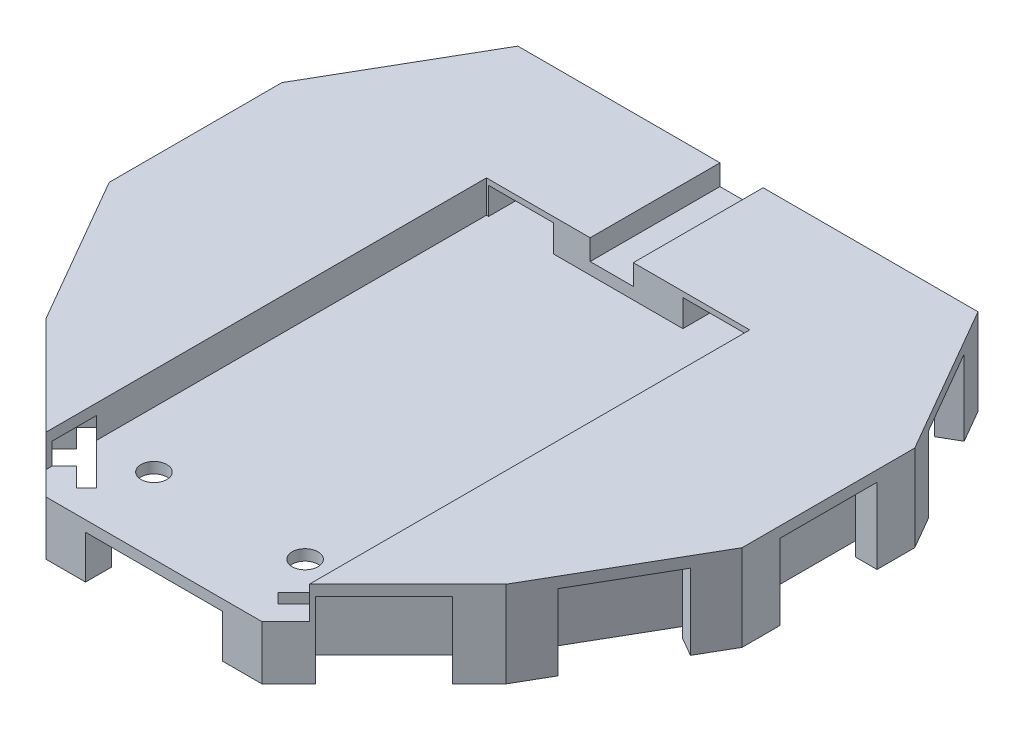
SolidWorks part; units mm, degrees
ref_plane "Front Plane" through (0, 0, 0) normal (0, 0, 1) x (1, 0, 0)
ref_plane "Top Plane" through (0, 0, 0) normal (0, 1, 0) x (1, 0, 0)
ref_plane "Right Plane" through (0, 0, 0) normal (1, 0, 0) x (0, 0, -1)
sketch "Sketch1" plane through (0, -12.45, 0) normal (0, -1, 0) x (1, 0, 0)
  line L0 (-7.62, 25.4) -> (-13.123, 25.4) construction
  line L1 (-18.0975, -36.83) -> (18.0975, -36.83) construction
  line L2 (-18.0975, -36.83) -> (-18.0975, 19.05) construction
  line L3 (-18.0975, 19.05) -> (18.0975, 19.05) construction
  line L4 (18.0975, -36.83) -> (18.0975, 19.05) construction
  line L5 (-18.0975, -36.83) -> (18.0975, 19.05) construction
  line L6 (-18.0975, 19.05) -> (18.0975, -36.83) construction
  line L7 (0, 0) -> (0, 31.75) construction
  line L8 (-12.7, 31.75) -> (12.7, 31.75)
  line L9 (12.7, 31.75) -> (27.0684, 17.3816)
  line L10 (-12.7, 31.75) -> (-27.0684, 17.3816)
  line L11 (27.0684, 17.3816) -> (37.2284, -0.216)
  line L12 (-27.0684, 17.3816) -> (-37.2284, -0.216)
  line L13 (37.2284, -0.216) -> (37.2284, -20.536)
  line L14 (-37.2284, -0.216) -> (-37.2284, -20.536)
  line L15 (37.2284, -20.536) -> (27.0684, -38.1337)
  line L16 (-37.2284, -20.536) -> (-27.0684, -38.1337)
  line L17 (14.047, 26.8109) -> (22.1293, 18.7286)
  line L18 (14.047, 26.8109) -> (17.6391, 30.403)
  line L19 (22.1293, 18.7286) -> (25.7214, 22.3207)
  line L20 (17.6391, 30.403) -> (25.7214, 22.3207)
  line L21 (14.047, 26.8109) -> (25.7214, 22.3207) construction
  line L22 (22.1293, 18.7286) -> (17.6391, 30.403) construction
  line L23 (-14.047, 26.8109) -> (-25.7214, 22.3207) construction
  line L24 (-22.1293, 18.7286) -> (-17.6391, 30.403) construction
  line L25 (-14.047, 26.8109) -> (-22.1293, 18.7286)
  line L26 (-14.047, 26.8109) -> (-17.6391, 30.403)
  line L27 (-17.6391, 30.403) -> (-25.7214, 22.3207)
  line L28 (-22.1293, 18.7286) -> (-25.7214, 22.3207)
  line L29 (27.0912, 12.2621) -> (32.8062, 2.3634)
  line L30 (27.0912, 12.2621) -> (31.4906, 14.8021)
  line L31 (32.8062, 2.3634) -> (37.2056, 4.9034)
  line L32 (31.4906, 14.8021) -> (37.2056, 4.9034)
  line L33 (27.0912, 12.2621) -> (37.2056, 4.9034) construction
  line L34 (32.8062, 2.3634) -> (31.4906, 14.8021) construction
  line L35 (-27.0912, 12.2621) -> (-37.2056, 4.9034) construction
  line L36 (-32.8062, 2.3634) -> (-31.4906, 14.8021) construction
  line L37 (-27.0912, 12.2621) -> (-32.8062, 2.3634)
  line L38 (-27.0912, 12.2621) -> (-31.4906, 14.8021)
  line L39 (-31.4906, 14.8021) -> (-37.2056, 4.9034)
  line L40 (-32.8062, 2.3634) -> (-37.2056, 4.9034)
  line L41 (34.6884, -4.661) -> (34.6884, -16.091)
  line L42 (34.6884, -4.661) -> (39.7684, -4.661)
  line L43 (34.6884, -16.091) -> (39.7684, -16.091)
  line L44 (39.7684, -4.661) -> (39.7684, -16.091)
  line L45 (34.6884, -4.661) -> (39.7684, -16.091) construction
  line L46 (34.6884, -16.091) -> (39.7684, -4.661) construction
  line L47 (-34.6884, -4.661) -> (-39.7684, -16.091) construction
  line L48 (-34.6884, -16.091) -> (-39.7684, -4.661) construction
  line L49 (-34.6884, -4.661) -> (-34.6884, -16.091)
  line L50 (-34.6884, -4.661) -> (-39.7684, -4.661)
  line L51 (-39.7684, -4.661) -> (-39.7684, -16.091)
  line L52 (-34.6884, -16.091) -> (-39.7684, -16.091)
  line L53 (32.8062, -23.1155) -> (27.0912, -33.0142)
  line L54 (32.8062, -23.1155) -> (37.2056, -25.6555)
  line L55 (27.0912, -33.0142) -> (31.4906, -35.5542)
  line L56 (37.2056, -25.6555) -> (31.4906, -35.5542)
  line L57 (32.8062, -23.1155) -> (31.4906, -35.5542) construction
  line L58 (27.0912, -33.0142) -> (37.2056, -25.6555) construction
  line L59 (-32.8062, -23.1155) -> (-31.4906, -35.5542) construction
  line L60 (-27.0912, -33.0142) -> (-37.2056, -25.6555) construction
  line L61 (-32.8062, -23.1155) -> (-27.0912, -33.0142)
  line L62 (-32.8062, -23.1155) -> (-37.2056, -25.6555)
  line L63 (-37.2056, -25.6555) -> (-31.4906, -35.5542)
  line L64 (-27.0912, -33.0142) -> (-31.4906, -35.5542)
  line L65 (11.8379, 29.02) -> (24.3384, 16.5195)
  line L66 (11.8379, 29.02) -> (10.6705, 27.8526)
  line L67 (24.3384, 16.5195) -> (23.171, 15.3521)
  line L68 (10.6705, 27.8526) -> (23.171, 15.3521)
  line L69 (-11.8379, 29.02) -> (-24.3384, 16.5195)
  line L70 (-11.8379, 29.02) -> (-10.6705, 27.8526)
  line L71 (-10.6705, 27.8526) -> (-23.171, 15.3521)
  line L72 (-24.3384, 16.5195) -> (-23.171, 15.3521)
  line L73 (25.5291, 14.9677) -> (34.3683, -0.3422)
  line L74 (25.5291, 14.9677) -> (24.0993, 14.1422)
  line L75 (34.3683, -0.3422) -> (32.9385, -1.1677)
  line L76 (24.0993, 14.1422) -> (32.9385, -1.1677)
  line L77 (-25.5291, 14.9677) -> (-34.3683, -0.3422)
  line L78 (-25.5291, 14.9677) -> (-24.0993, 14.1422)
  line L79 (-24.0993, 14.1422) -> (-32.9385, -1.1677)
  line L80 (-34.3683, -0.3422) -> (-32.9385, -1.1677)
  line L81 (34.6884, -1.5368) -> (34.6884, -19.2152)
  line L82 (34.6884, -1.5368) -> (33.0374, -1.5368)
  line L83 (34.6884, -19.2152) -> (33.0374, -19.2152)
  line L84 (33.0374, -1.5368) -> (33.0374, -19.2152)
  line L85 (-34.6884, -1.5368) -> (-34.6884, -19.2152)
  line L86 (-34.6884, -1.5368) -> (-33.0374, -1.5368)
  line L87 (-33.0374, -1.5368) -> (-33.0374, -19.2152)
  line L88 (-34.6884, -19.2152) -> (-33.0374, -19.2152)
  line L89 (25.5291, -35.7198) -> (34.3683, -20.4099)
  line L90 (25.5291, -35.7198) -> (24.0993, -34.8943)
  line L91 (34.3683, -20.4099) -> (32.9385, -19.5844)
  line L92 (24.0993, -34.8943) -> (32.9385, -19.5844)
  line L93 (-25.5291, -35.7198) -> (-34.3683, -20.4099)
  line L94 (-25.5291, -35.7198) -> (-24.0993, -34.8943)
  line L95 (-24.0993, -34.8943) -> (-32.9385, -19.5844)
  line L96 (-34.3683, -20.4099) -> (-32.9385, -19.5844)
  line L97 (-27.0684, -38.1337) -> (27.0684, -38.1337)
  point P6 (19.8842, 24.5658)
  point P21 (32.1484, 8.5828)
  point P22 (37.2284, -10.376)
  point P23 (0, -8.89)
  point P32 (-19.8842, 24.5658)
  point P33 (32.1484, -29.3349)
  point P42 (-32.1484, 8.5828)
  point P52 (-37.2284, -10.376)
  point P62 (-32.1484, -29.3349)
  point P92 (18.0882, 22.7697)
  point P93 (29.9487, 7.3128)
  point P94 (34.6884, -10.376)
  point P95 (29.9487, -28.0649)
  line M56 (15.24, 25.4) -> (7.62, 25.4)
  line M57 (7.62, 25.4) -> (7.62, 23.7024)
  arc M58 (7.62, 23.7024) -> (7.62, 22.0176) centre (8.89, 22.86) cw
  line M59 (7.62, 22.0176) -> (7.62, -22.86)
  line M60 (7.62, -22.86) -> (15.24, -22.86)
  line M61 (15.24, -22.86) -> (15.24, 25.4)
  dimension "D1" = 55.88
  dimension "D2" = 36.195
  dimension "D3" = 6.35
  dimension "D4" = 45
  dimension "D5" = 30
  dimension "D6" = 30
  dimension "D7" = 20.32
  dimension "D8" = 6.35
  dimension "D9" = 11.43
  dimension "D10" = 2.54
  dimension "D11" = 17.6784
  dimension "D12" = 1.651
  dimension "D13" = 25.4
extrude "Boss-Extrude1" add sketch "Sketch1" against normal blind 3.81 contours L16 L97 L15 L55 L89 L90 L92 L91 L54 L13 L43 L81 L83 L84 L82 L42 L11 L31 L73 L75 L76 L74 L30 L9 L19 L65 L67 L68 L66 L18 L8 L10 L26 L69 L70 L71 M61 M60 M59 M58 M57 M56 | L85 L88 L87 L86 L49 | L52 L49 L50 L14 | L77 L80 L79 L78 L37 | L40 L37 L38 L12 | L69 L72 L71 L70 L25 | L28 L25 L26 L10 | L68 M56 M57 M58 M59 M60 M61 | L68 M56 M61 | L66 L68 L67 L65 L17 M56 M61 | L17 L19 L9 L18 | L74 L76 L75 L73 L29 | L29 L31 L11 L30 | L82 L84 L83 L81 L41 | L41 L43 L13 L42 | L92 L90 L89 L53 L91 | L53 L55 L15 L54 | L96 L93 L61 L94 L95 | L64 L61 L62 L16 region at (-1.166, -12.45, -7.077) region at (-18.9862, -12.45, 23.6678) region at (18.9862, -12.45, 23.6678) region at (-17.5044, -12.45, 22.186) region at (17.7514, -12.45, 21.9774) region at (-31.0486, -12.45, 7.9478) region at (31.0486, -12.45, 7.9478) region at (-29.2338, -12.45, 6.9) region at (29.2338, -12.45, 6.9) region at (14.5343, -12.45, 24.6943) region at (11.4591, -12.45, 0.7016) region at (-35.9584, -12.45, -10.376) region at (35.9584, -12.45, -10.376) region at (-33.8629, -12.45, -10.376) region at (33.8629, -12.45, -10.376) region at (-31.0486, -12.45, -28.6999) region at (31.0486, -12.45, -28.6999) region at (-29.2338, -12.45, -27.6521) region at (29.2338, -12.45, -27.6521)
sketch "Sketch2" plane through (0, -12.45, 0) normal (0, -1, 0) x (1, 0, 0)
  line L0 (-7.62, 25.4) -> (-13.123, 25.4) construction
  line L1 (-15.24, 25.4) -> (15.24, 25.4)
  line L2 (-15.24, 25.4) -> (-15.24, -22.86)
  line L3 (-15.24, -22.86) -> (15.24, -22.86)
  line L4 (15.24, 25.4) -> (15.24, -22.86)
  line L5 (-15.24, 23.283) -> (-15.24, -22.86) construction
extrude "Cut-Extrude1" cut sketch "Sketch2" against normal blind 3.81
sketch "Sketch4" plane through (0, 0, 25.4) normal (0, 0, -1) x (-1, 0, 0)
  line L4 (-15.24, -12.45) -> (15.24, -12.45)
  line L5 (15.24, -12.45) -> (15.24, -8.64)
  line L6 (15.24, -8.64) -> (-15.24, -8.64)
  line L7 (-15.24, -8.64) -> (-15.24, -12.45)
  line L8 (-15.24, -12.45) -> (15.24, -12.45)
  line L9 (15.24, -12.45) -> (15.24, -8.64)
  line L10 (15.24, -8.64) -> (-15.24, -8.64)
  line L11 (-15.24, -8.64) -> (-15.24, -12.45)
  dimension "D1" = 0
extrude "Cut-Extrude2" cut sketch "Sketch4" against normal blind 27.94
sketch "Sketch5" plane through (0, 0, -22.86) normal (0, 0, 1) x (1, 0, 0)
  line L1 (-15.24, -8.64) -> (-15.49, -8.64)
  line L2 (-15.24, -8.64) -> (-15.24, -12.45)
  line L3 (-15.24, -12.45) -> (-15.49, -12.45)
  line L4 (-15.24, -12.45) -> (15.24, -12.45)
  line L5 (15.24, -12.45) -> (15.24, -8.64)
  line L6 (15.24, -8.64) -> (-15.24, -8.64)
  line L7 (-15.24, -8.64) -> (-15.24, -12.45)
  line L8 (-15.24, -12.45) -> (15.24, -12.45)
  line L9 (15.24, -12.45) -> (15.24, -8.64)
  line L10 (15.24, -8.64) -> (-15.24, -8.64)
  line L11 (-15.24, -8.64) -> (-15.24, -12.45)
  line L12 (-15.49, -8.64) -> (-15.49, -12.45)
  line L13 (15.24, -8.64) -> (15.49, -8.64)
  line L14 (15.24, -8.64) -> (15.24, -12.45)
  line L15 (15.24, -12.45) -> (15.49, -12.45)
  line L16 (15.49, -8.64) -> (15.49, -12.45)
  line M13 (-15.24, -8.64) -> (-15.24, -12.45)
  dimension "D2" = 0.25
  dimension "D3" = 0.25
  dimension "D1" = 0
extrude "Cut-Extrude3" cut sketch "Sketch5" along normal through all contours L1 L12 L3 M13 | L13 L16 L15 L14 region at (-15.365, -10.545, -22.86)
sketch "Sketch6" plane through (0, 0, -22.86) normal (0, 0, 1) x (1, 0, 0)
  line L0 (7.62, -12.45) -> (15.24, -12.45) construction
  line L1 (15.24, -9.275) -> (15.24, -12.45) construction
  line L2 (11.557, -9.275) -> (15.24, -9.275) construction
  line L3 (11.557, -9.275) -> (7.62, -9.275) construction
  line L4 (7.62, -9.275) -> (7.62, -12.45) construction
  line L5 (-15.24, -12.45) -> (-15.24, -9.275) construction
  line L6 (-15.24, -9.275) -> (-11.557, -9.275) construction
  line L7 (-11.557, -9.275) -> (-7.62, -9.275) construction
  line L8 (-7.62, -9.275) -> (-7.62, -12.45) construction
  line L9 (-15.24, -12.45) -> (-7.62, -12.45) construction
  line L10 (7.62, -12.45) -> (15.24, -12.45)
  line L11 (15.24, -9.275) -> (15.24, -12.45)
  line L12 (11.557, -9.275) -> (15.24, -9.275)
  line L13 (11.557, -9.275) -> (7.62, -9.275)
  line L14 (7.62, -9.275) -> (7.62, -12.45)
  line L15 (-15.24, -12.45) -> (-15.24, -9.275)
  line L16 (-15.24, -9.275) -> (-11.557, -9.275)
  line L17 (-11.557, -9.275) -> (-7.62, -9.275)
  line L18 (-7.62, -9.275) -> (-7.62, -12.45)
  line L19 (-15.24, -12.45) -> (-7.62, -12.45)
extrude "Cut-Extrude4" cut sketch "Sketch6" against normal blind 7.874
extrude "Boss-Extrude2" add sketch "Sketch1<3>" along normal blind 1.27 contours L8 L9 L11 L13 L15 L97 L16 L14 L12 L10
sketch "Sketch1<3>" plane through (0, -12.45, 0) normal (0, -1, 0) x (1, 0, 0) same geometry as "Sketch1"
sketch "Sketch7" plane through (0, -13.72, 0) normal (0, -1, 0) x (1, 0, 0)
  line L0 (0, 0) -> (0, 31.75) construction
  line L1 (0, 0) -> (0, 31.75)
  line L2 (-24.0993, -34.8943) -> (-32.9385, -19.5844) construction
  line L3 (-33.0374, -1.5368) -> (-33.0374, -19.2152) construction
  line L4 (-24.0993, 14.1422) -> (-32.9385, -1.1677) construction
  line L5 (-10.6705, 27.8526) -> (-23.171, 15.3521) construction
  line L6 (-8.043, 28.6839) -> (-8.043, 31.75)
  line L7 (-9.7724, 26.9545) -> (-8.043, 28.6839)
  line L8 (-9.7724, 26.9545) -> (-22.6985, 14.0285)
  line L9 (-22.6985, 14.0285) -> (-31.7674, -1.6793)
  line L10 (-31.7674, -1.6793) -> (-31.7674, -19.0728)
  line L11 (-20.7626, -38.1337) -> (-31.7674, -19.0728)
  line L12 (8.043, 28.6839) -> (8.043, 31.75)
  line L13 (9.7724, 26.9545) -> (8.043, 28.6839)
  line L14 (9.7724, 26.9545) -> (22.6985, 14.0285)
  line L15 (22.6985, 14.0285) -> (31.7674, -1.6793)
  line L16 (31.7674, -1.6793) -> (31.7674, -19.0728)
  line L17 (20.7626, -38.1337) -> (31.7674, -19.0728)
  line L18 (20.7626, -38.1337) -> (27.0684, -38.1337)
  line L19 (20.7626, -38.1337) -> (27.0684, -38.1337)
  line L20 (-8.043, 31.75) -> (-12.7, 31.75)
  line L21 (-21.1292, -37.4987) -> (-31.7674, -19.0728) construction
  line L23 (-12.7, 31.75) -> (-27.0684, 17.3816)
  line L24 (-27.0684, 17.3816) -> (-37.2284, -0.216)
  line L25 (-22.2291, -38.1337) -> (-33.0374, -19.4131) construction
  line L26 (-33.0374, -1.339) -> (-33.0374, -19.4131) construction
  line L27 (-23.7148, 14.8083) -> (-33.0374, -1.339) construction
  line L28 (-10.6705, 27.8526) -> (-23.7148, 14.8083)
  line L29 (-10.6705, 27.8526) -> (-9.313, 29.21) construction
  line L31 (-9.313, 29.21) -> (-9.313, 31.75) construction
  line L32 (-12.7, 31.75) -> (12.7, 31.75) construction
  line L34 (-27.0684, -38.1337) -> (27.0684, -38.1337) construction
  line L35 (-27.0684, -38.1337) -> (-20.7626, -38.1337)
  line L36 (-37.2284, -0.216) -> (-37.2284, -20.536)
  line L37 (-37.2284, -20.536) -> (-27.0684, -38.1337)
  line L38 (-27.0684, -38.1337) -> (27.0684, -38.1337)
  line L39 (27.0684, -38.1337) -> (37.2284, -20.536)
  line L40 (37.2284, -20.536) -> (37.2284, -0.216)
  line L41 (37.2284, -0.216) -> (27.0684, 17.3816)
  line L42 (27.0684, 17.3816) -> (12.7, 31.75)
  line L43 (12.7, 31.75) -> (-12.7, 31.75)
  line L44 (-12.7, 31.75) -> (-27.0684, 17.3816)
  line L45 (-27.0684, 17.3816) -> (-37.2284, -0.216)
  line L46 (-37.2284, -0.216) -> (-37.2284, -20.536)
  line L47 (-37.2284, -20.536) -> (-27.0684, -38.1337)
  line L48 (-27.0684, -38.1337) -> (-20.7626, -38.1337)
  line L49 (27.0684, -38.1337) -> (37.2284, -20.536)
  line L50 (37.2284, -20.536) -> (37.2284, -0.216)
  line L51 (37.2284, -0.216) -> (27.0684, 17.3816)
  line L52 (27.0684, 17.3816) -> (12.7, 31.75)
  line L53 (12.7, 31.75) -> (8.043, 31.75)
  line M19 (-27.0684, -38.1337) -> (27.0684, -38.1337)
  line M20 (27.0684, -38.1337) -> (37.2284, -20.536)
  line M21 (37.2284, -20.536) -> (37.2284, -0.216)
  line M22 (37.2284, -0.216) -> (27.0684, 17.3816)
  line M23 (27.0684, 17.3816) -> (12.7, 31.75)
  line M24 (12.7, 31.75) -> (-12.7, 31.75)
  dimension "D1" = 2.54
  dimension "D2" = 1.27
  dimension "D3" = 0
extrude "Boss-Extrude3" add sketch "Sketch7" along normal blind 5.08 contours L17 L12 L13 L14 L15 L16 M19 M20 M21 M22 M23 M24 | L11 L10 L9 L8 L7 L6 region at (-9.4432, -13.72, 28.3548) region at (10.3715, -13.72, 30.9927)
extrude "Cut-Extrude5" cut sketch "Sketch1<4>" against normal offset from surface 1.27 and the other way through all contours L96 L93 L61 L94 L95 | L64 L61 L62 L16 | L52 L49 L50 L14 | L85 L88 L87 L86 L49 | L77 L80 L79 L78 L37 | L40 L37 L38 L12 | L69 L72 L71 L70 L25 | L28 L25 L26 L10 | L68 M56 M61 | L66 L68 L67 L65 L17 M56 M61 | L17 L19 L9 L18 | L74 L76 L75 L73 L29 | L29 L31 L11 L30 | L82 L84 L83 L81 L41 | L41 L43 L13 L42 | L92 L90 L89 L53 L91 | L53 L55 L15 L54 region at (-18.9862, -12.45, 23.6678) region at (18.9862, -12.45, 23.6678) region at (-17.5044, -12.45, 22.186) region at (17.7514, -12.45, 21.9774) region at (-31.0486, -12.45, 7.9478) region at (31.0486, -12.45, 7.9478) region at (-29.2338, -12.45, 6.9) region at (29.2338, -12.45, 6.9) region at (14.5343, -12.45, 24.6943) region at (-35.9584, -12.45, -10.376) region at (35.9584, -12.45, -10.376) region at (-33.8629, -12.45, -10.376) region at (33.8629, -12.45, -10.376) region at (-31.0486, -12.45, -28.6999) region at (31.0486, -12.45, -28.6999) region at (-29.2338, -12.45, -27.6521) region at (29.2338, -12.45, -27.6521) up to face at (0, -8.64, -5.9007)
sketch "Sketch1<4>" plane through (0, -12.45, 0) normal (0, -1, 0) x (1, 0, 0) same geometry as "Sketch1"
sketch "Sketch8" plane through (0, -13.72, 0) normal (0, -1, 0) x (1, 0, 0)
  circle A0 centre (-8.89, 22.86) radius 1.524 construction
  circle A1 centre (8.89, 22.86) radius 1.524 construction
  circle A2 centre (-8.89, 22.86) radius 1.524
  circle A3 centre (8.89, 22.86) radius 1.524
extrude "Cut-Extrude6" cut sketch "Sketch8" against normal through all contours A2 | A3
sketch "Sketch9" plane through (0, 0, -38.1337) normal (0, 0, -1) x (-1, 0, 0)
  line L0 (0.7493, -9.3502) -> (0.7493, -7.7002) construction
  line L1 (-1.7907, -5.9852) -> (3.2893, -5.9852)
  line L2 (-1.7907, -5.9852) -> (-1.7907, -11.0652)
  line L3 (-1.7907, -11.0652) -> (3.2893, -11.0652)
  line L4 (3.2893, -5.9852) -> (3.2893, -11.0652)
  line L5 (-1.7907, -5.9852) -> (3.2893, -11.0652) construction
  line L6 (-1.7907, -11.0652) -> (3.2893, -5.9852) construction
  point P0 (0.7493, -8.5252)
  dimension "D1" = 5.08
  dimension "D2" = 5.08
extrude "Cut-Extrude7" cut sketch "Sketch9" against normal through all
